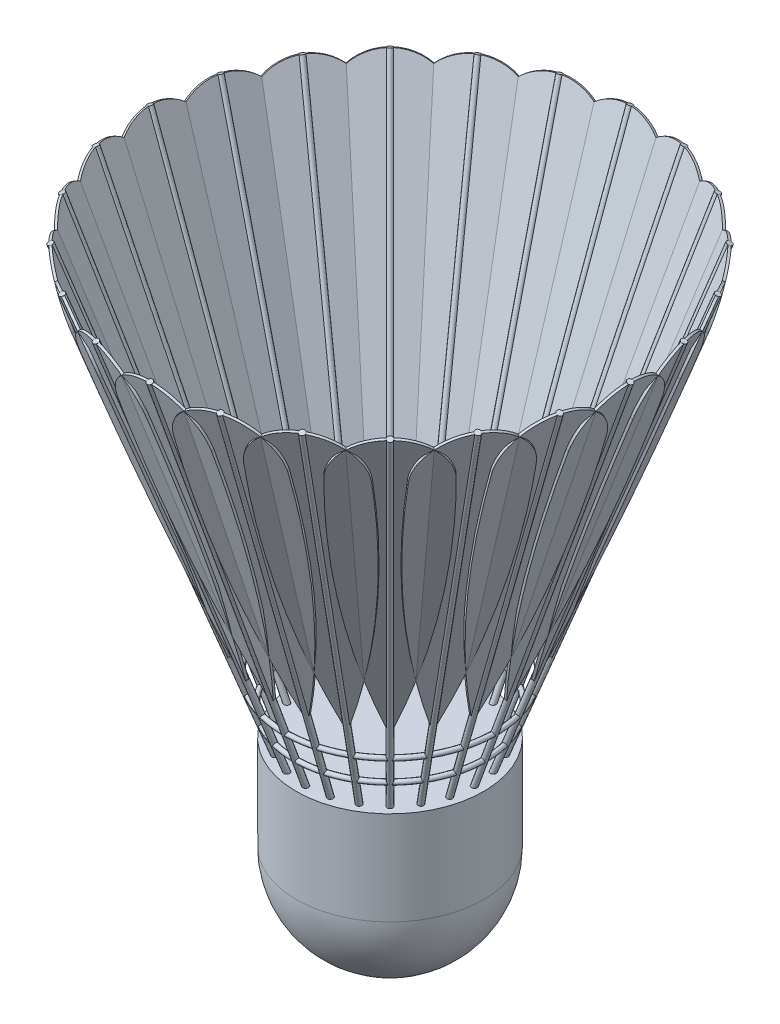
SolidWorks part; units mm, degrees
ref_plane "Front Plane" through (0, 0, 0) normal (0, 0, 1) x (1, 0, 0)
ref_plane "Top Plane" through (0, 0, 0) normal (0, 1, 0) x (1, 0, 0)
ref_plane "Right Plane" through (0, 0, 0) normal (1, 0, 0) x (0, 0, -1)
sketch "Sketch2" plane through (0, 0, 0) normal (0, 0, 1) x (1, 0, 0)
  line L0 (0, 0) -> (0, -20)
  line L2 (10, -10) -> (10, 0)
  line L3 (10, 0) -> (0, 0)
  arc A0 (0, -20) -> (10, -10) centre (0, -10) ccw
  dimension "D2" = 10
  dimension "D1" = 20
revolve "Revolve1" add sketch "Sketch2" angle 360 about L0
sketch "Sketch3" plane through (0, 0, 0) normal (0, 0, 1) x (1, 0, 0)
  line L1 (0, 0) -> (10, 0) construction
sketch "Sketch4" plane through (0, 0, 0) normal (0, 1, 0) x (1, 0, 0)
  line L0 (9, 4.0024) -> (9, -3.9745) construction
  dimension "D1" = 9
ref_plane "Plane1" through (0, 0, 0) normal (0, -1, 0) x (-1, 0, 0)
ref_plane "Plane2" through (0, -2, 0) normal (0, -1, 0) x (-1, 0, 0)
ref_plane "Plane3" through (7.9472, -2.8925, 0) normal (0.9397, -0.342, 0) x (-0.342, -0.9397, 0)
sketch "Sketch5" plane through (7.9472, -2.8925, 0) normal (0.9397, -0.342, 0) x (-0.342, -0.9397, 0)
  line L0 (-1.7101, 0) -> (-51.7101, 0)
  line L1 (0, 0) -> (-3.4202, 0) construction
  dimension "D1" = 50
sketch "Sketch6" plane through (7.9472, -2.8925, 0) normal (0.9397, -0.342, 0) x (-0.342, -0.9397, 0)
  line L1 (-1.7101, 0.3) -> (-1.7101, 0)
  line L2 (-1.7101, 0.3) -> (-51.7101, 0.3)
  line L3 (-1.7101, 0.3) -> (-51.7101, 0.3)
  line L4 (-1.7101, 0) -> (-51.7101, 0)
  line L5 (-51.7101, 0) -> (-51.7101, 0.3)
  dimension "D1" = 0.3
revolve "Revolve2" add sketch "Sketch6" angle 360 about L4
sketch "Sketch7" plane through (7.9472, -2.8925, 0) normal (0.9397, -0.342, 0) x (-0.342, -0.9397, 0)
  line L1 (-1.7101, 0) -> (-51.7101, 0) construction
  line L2 (-46.7101, 5) -> (-28.7279, 5) construction
  line L3 (-28.7279, 5) -> (-12.7101, 0) construction
  line L4 (-46.7101, -5) -> (-28.7279, -5) construction
  line L5 (-28.7279, -5) -> (-12.7101, 0) construction
  arc A0 (-46.7101, -5) -> (-46.7101, 5) centre (-46.7101, 0) cw
  spline S0 degree 2 poles (-46.7101, 5) (-28.7279, 5) (-12.7101, 0) knots 0 0 0 1 1 1
  spline S1 degree 2 poles (-46.7101, -5) (-28.7279, -5) (-12.7101, 0) knots 0 0 0 1 1 1
  dimension "D1" = 5
  dimension "D2" = 5
extrude "Boss-Extrude1" add sketch "Sketch7" along normal blind 0.13 and the other way blind 0.13
sketch "Sketch10" plane through (0, 0, 0) normal (1, 0, 0) x (0, 0, -1)
  line L0 (0, 0) -> (0, 54.6521) construction
sketch "Sketch12" plane through (0, 0, 0) normal (0, 1, 0) x (1, 0, 0)
  circle A0 centre (0, 0) radius 9 construction
pattern_circular "CirPattern2" count 25 every 15 about axis through (0, 0, 0) along (0, 1, 0) of "Boss-Extrude1", "Revolve2"
ref_plane "Plane4" through (0, 0, 0) normal (0, 0, -1) x (0, 1, 0)
sketch "Sketch14" plane through (0, 0, 0) normal (0, 0, -1) x (0, 1, 0)
  line L0 (3.0092, 10.0953) -> (6.0092, 11.1872) construction
  line L1 (-1.2856, 8.5321) -> (45.6991, 25.6331) construction
  circle A0 centre (6.0092, 11.1872) radius 0.25
  circle A1 centre (3.0092, 10.0953) radius 0.25
  dimension "D1" = 0.5
  dimension "D2" = 0.5
  dimension "D3" = 3
revolve "Revolve3" add sketch "Sketch14" angle 360 about L0
